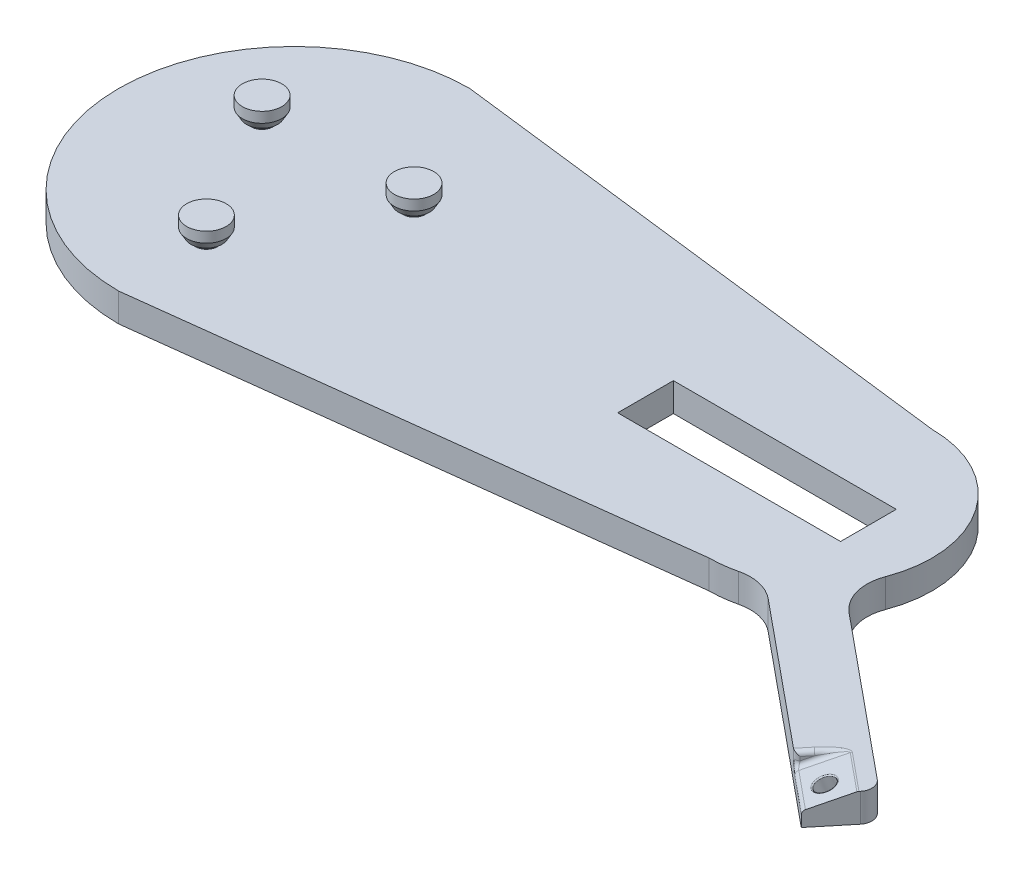
SolidWorks part; units mm, degrees
ref_plane "Front Plane" through (0, 0, 0) normal (0, 0, 1) x (1, 0, 0)
ref_plane "Top Plane" through (0, 0, 0) normal (0, 1, 0) x (1, 0, 0)
ref_plane "Right Plane" through (0, 0, 0) normal (1, 0, 0) x (0, 0, -1)
sketch "Sketch1" plane through (0, 0, 0) normal (0, 1, 0) x (1, 0, 0)
  circle A0 centre (0, 0) radius 20
  circle A1 centre (0, -20) radius 2.5
  circle A2 centre (0, 0) radius 20
  circle A3 centre (-17.3205, 10) radius 2.5
  circle A4 centre (0, 0) radius 20
  circle A5 centre (17.3205, 10) radius 2.5
  circle A6 centre (0, 0) radius 16.8092
  circle A7 centre (0, 0) radius 25
  dimension "D1" = 40
  dimension "D2" = 5
  dimension "D4" = 50
  dimension "D3" = 3
extrude "Boss-Extrude1" add sketch "Sketch1" along normal blind 3 contours A7 A5 A0 A1 A3 | A5 A0 A3 A1 A6
sketch "Sketch2" plane through (0, 3, 0) normal (0, 1, 0) x (1, 0, 0)
  circle A0 centre (0, -20) radius 2.5
  circle A1 centre (17.3205, 10) radius 2.5
  circle A2 centre (-17.3205, 10) radius 2.5
extrude "Boss-Extrude2" add sketch "Sketch2" along normal blind 5 and the other way blind 3
sketch "Sketch3" plane through (0, 8, 0) normal (0, 1, 0) x (1, 0, 0)
  circle A0 centre (-17.3205, 10) radius 65.4137
extrude "Cut-Extrude1" cut sketch "Sketch3" against normal blind 3.5
sketch "Sketch4" plane through (0, 4.5, 0) normal (0, 1, 0) x (1, 0, 0)
  circle A6 centre (0, -20) radius 4.5
  circle A7 centre (-17.3205, 10) radius 4.5
  circle A8 centre (17.3205, 10) radius 4.5
  dimension "D2" = 9
  dimension "D3" = 9
  dimension "D4" = 9
extrude "Boss-Extrude5" add sketch "Sketch4" along normal blind 4
chamfer "Chamfer2" distance 0.5 angle 60 3 edges at (17.3205, 4.5, -7.5) (-17.3205, 4.5, -7.5) (0, 4.5, 22.5)
chamfer "Chamfer3" distance 0.94 angle 60 3 edges at (0, 4.5, 24.5) (-17.3205, 4.5, -5.5) (17.3205, 4.5, -5.5)
sketch "Sketch5" plane through (0, 0, 0) normal (0, -1, 0) x (1, 0, 0)
  line L0 (0, 0) -> (120, 0)
  line L1 (120, 25.4) -> (0, 40)
  line L2 (120, -25.4) -> (0, -40)
  circle A0 centre (0, 0) radius 40
  circle A1 centre (120, 0) radius 25.4
  circle A2 centre (120, 0) radius 25.4
  circle A3 centre (0, 0) radius 40
  dimension "D1" = 80
  dimension "D3" = 50.8
  dimension "D2" = 120
extrude "Boss-Extrude9" add sketch "Sketch5" against normal blind 3
sketch "Sketch7" plane through (0, 0, 0) normal (0, -1, 0) x (1, 0, 0)
  line L2 (0, -40) -> (120, -25.4)
  line L3 (120, 25.4) -> (0, 40)
  line L4 (0, -40) -> (120, -25.4)
  line L5 (120, 25.4) -> (0, 40)
  arc A2 (120, -25.4) -> (120, 25.4) centre (120, 0) ccw
  arc A3 (0, 40) -> (0, -40) centre (0, 0) ccw
  arc A4 (120, -25.4) -> (120, 25.4) centre (120, 0) ccw
  arc A5 (0, 40) -> (0, -40) centre (0, 0) ccw
  dimension "D1" = 0
extrude "Boss-Extrude10" add sketch "Sketch7" along normal blind 3
sketch "Sketch8" plane through (0, -3, 0) normal (0, -1, 0) x (1, 0, 0)
  line L1 (131.6955, 7.1677) -> (80.8955, 7.1677)
  line L2 (131.6955, 7.1677) -> (131.6955, -5.5323)
  line L3 (131.6955, -5.5323) -> (80.8955, -5.5323)
  line L4 (80.8955, 7.1677) -> (80.8955, -5.5323)
  line L5 (131.6955, 7.1677) -> (80.8955, -5.5323) construction
  line L6 (131.6955, -5.5323) -> (80.8955, 7.1677) construction
  point P0 (106.2955, 0.8177)
  dimension "D1" = 50.8
  dimension "D2" = 12.7
extrude "Cut-Extrude2" cut sketch "Sketch8" against normal blind 34
sketch "Sketch9" plane through (0, 3, 0) normal (0, 1, 0) x (1, 0, 0)
  line L2 (120, 25.4) -> (0, 40)
  line L3 (0, -40) -> (120, -25.4)
  line L4 (120, 25.4) -> (0, 40)
  line L5 (0, -40) -> (120, -25.4)
  line L8 (80.8955, 5.5323) -> (80.8955, -7.1677)
  line L9 (131.6955, 5.5323) -> (80.8955, 5.5323)
  line L10 (131.6955, -7.1677) -> (131.6955, 5.5323)
  line L11 (80.8955, -7.1677) -> (131.6955, -7.1677)
  line L12 (80.8955, 5.5323) -> (80.8955, -7.1677)
  line L13 (131.6955, 5.5323) -> (80.8955, 5.5323)
  line L14 (131.6955, -7.1677) -> (131.6955, 5.5323)
  line L15 (80.8955, -7.1677) -> (131.6955, -7.1677)
  circle A1 centre (17.3205, 10) radius 2.5
  arc A2 (0, 40) -> (0, -40) centre (0, 0) ccw
  arc A3 (120, -25.4) -> (120, 25.4) centre (120, 0) ccw
  arc A4 (0, 40) -> (0, -40) centre (0, 0) ccw
  arc A5 (120, -25.4) -> (120, 25.4) centre (120, 0) ccw
  circle A6 centre (17.3205, 10) radius 2.5
  circle A7 centre (0, -20) radius 2.5
  circle A8 centre (0, -20) radius 2.5
  circle A9 centre (-17.3205, 10) radius 2.5
  circle A10 centre (-17.3205, 10) radius 2.5
  dimension "D1" = 0
  dimension "D2" = 0
  dimension "D3" = 0
  dimension "D4" = 0
  dimension "D5" = 0
extrude "Boss-Extrude12" add sketch "Sketch9" along normal blind 0.5
sketch "Sketch11" plane through (0, 3.5, 0) normal (0, 1, 0) x (1, 0, 0)
  line L0 (129.6123, -14.341) -> (181.1858, -56.7404) construction
  line L1 (133.6113, -9.4768) -> (185.1848, -51.8762)
  line L2 (125.6133, -19.2053) -> (177.1869, -61.6047)
  arc A0 (133.6113, -9.4768) -> (125.6133, -19.2053) centre (129.6123, -14.341) ccw
  arc A1 (177.1869, -61.6047) -> (185.1848, -51.8762) centre (181.1858, -56.7404) ccw
  point P2 (155.3991, -35.5407)
extrude "Boss-Extrude14" add sketch "Sketch11" against normal up to surface (6.5 mm away) up to face at (106.2955, -3, 0.8177)
sketch "Sketch15" plane through (0, 3.5, 0) normal (0, 1, 0) x (1, 0, 0)
  line L0 (185.1848, -51.8762) -> (177.1869, -61.6047)
  line L1 (177.1869, -61.6047) -> (186.4597, -79.1475)
  line L2 (186.4597, -79.1475) -> (194.1189, -68.9714)
  line L3 (194.1189, -68.9714) -> (191.8217, -55.4283)
  line L4 (191.8217, -55.4283) -> (187.4829, -50.2791)
  line L5 (187.4829, -50.2791) -> (185.1848, -51.8762)
extrude "Cut-Extrude8" cut sketch "Sketch15" against normal blind 12
sketch "Sketch16" plane through (135.9488, 0, 111.7656) normal (0.7725, 0, 0.6351) x (0.6351, 0, -0.7725)
  line L0 (74.0992, 3.5) -> (64.9361, 0.25)
  line L1 (77.5302, 3.5) -> (64.9361, 3.5) construction
  line L2 (64.9361, -3) -> (64.9361, 3.5) construction
  line L3 (64.9361, 0.25) -> (62.6763, 5.4818)
  line L4 (62.6763, 5.4818) -> (67.1946, 6.3466)
  line L5 (67.1946, 6.3466) -> (74.0992, 3.5)
extrude "Cut-Extrude9" cut sketch "Sketch16" against normal blind 12
sketch "Sketch17" plane through (4.5581, -20.2361, -5.5443) normal (-0.2123, 0.9425, 0.2582) x (0.9772, 0.2047, 0.0561)
  circle A0 centre (175.4194, -52.6514) radius 2.1
  dimension "D1" = 4.2
extrude "Cut-Extrude10" cut sketch "Sketch17" against normal blind 12
fillet "Fillet3" radius 1 5 edges at (178.3711, 3.5, 50.7162) (172.5521, 0.25, 57.7943) (170.8268, 3.5, 50.4449) (167.9173, 1.875, 53.984) (170.8268, 1.875, 50.4449)
fillet "Fillet4" radius 0.25 1 edges at (175.9792, 1.2118, 57.1012)
fillet "Fillet5" radius 10 2 edges at (130.4258, 0.25, 23.1617) (140.4345, 0.25, 15.0862)
fillet "Fillet6" radius 3 1 edges at (185.1848, 0.25, 51.8762)
fillet "Fillet7" radius 0.25 1 edges at (175.6379, -3, 55.491)
